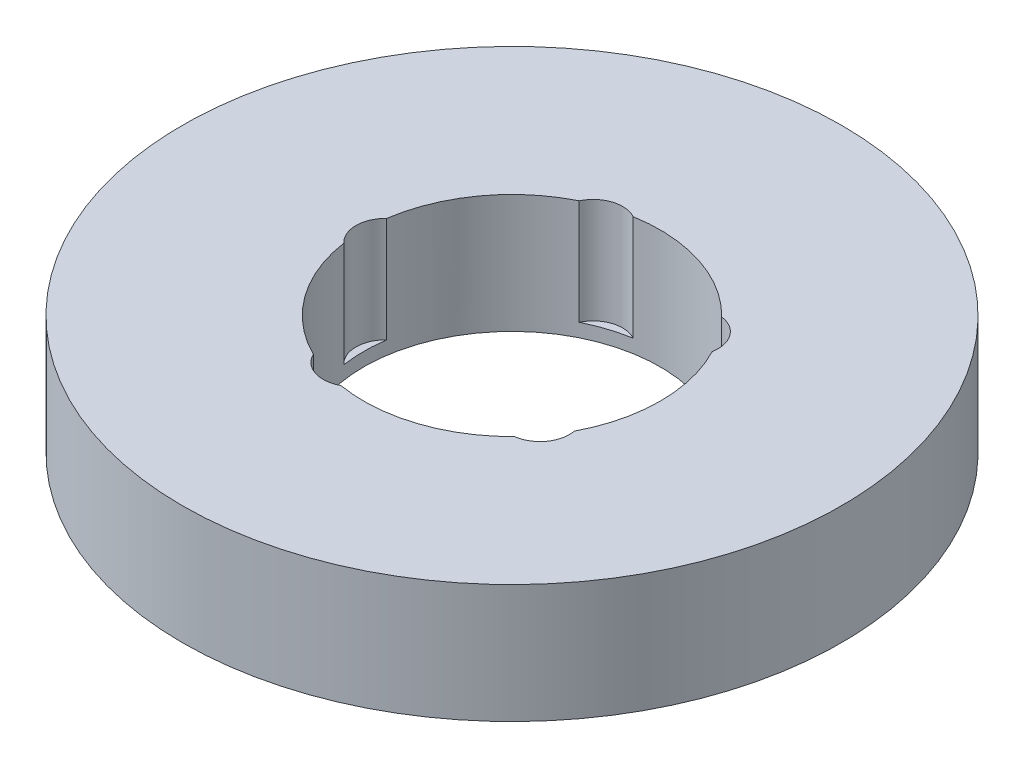
SolidWorks part; units mm, degrees
ref_plane "Front Plane" through (0, 0, 0) normal (0, 0, 1) x (1, 0, 0)
ref_plane "Top Plane" through (0, 0, 0) normal (0, 1, 0) x (1, 0, 0)
ref_plane "Right Plane" through (0, 0, 0) normal (1, 0, 0) x (0, 0, -1)
sketch "Sketch1" plane through (0, 0, 0) normal (0, 1, 0) x (1, 0, 0)
  circle A0 centre (0, 0) radius 50
  dimension "FLANGE_OD" = 100
extrude "Boss-Extrude1" add sketch "Sketch1" along normal blind 18
sketch "Sketch2" plane through (0, 0, 0) normal (0, 1, 0) x (1, 0, 0)
  circle A0 centre (0, 0) radius 22.5
  dimension "BORE_D" = 45
extrude "Cut-Extrude1" cut sketch "Sketch2" along normal through all
sketch "Sketch3" plane through (0, 18, 0) normal (0, 1, 0) x (1, 0, 0)
  circle A0 centre (0, 0) radius 19.1853 construction
  circle A1 centre (-19.1853, 0) radius 4.4792
  dimension "BOLT_D" = 8.9584
  dimension "BOLT_PCD" = 38.3705
extrude "Cut-Extrude2" cut sketch "Sketch3" against normal blind 15.9617
pattern_circular "CirPattern1" count 5 over 360 about axis through (0, 0, 0) along (0, 1, 0) of "Cut-Extrude2"
